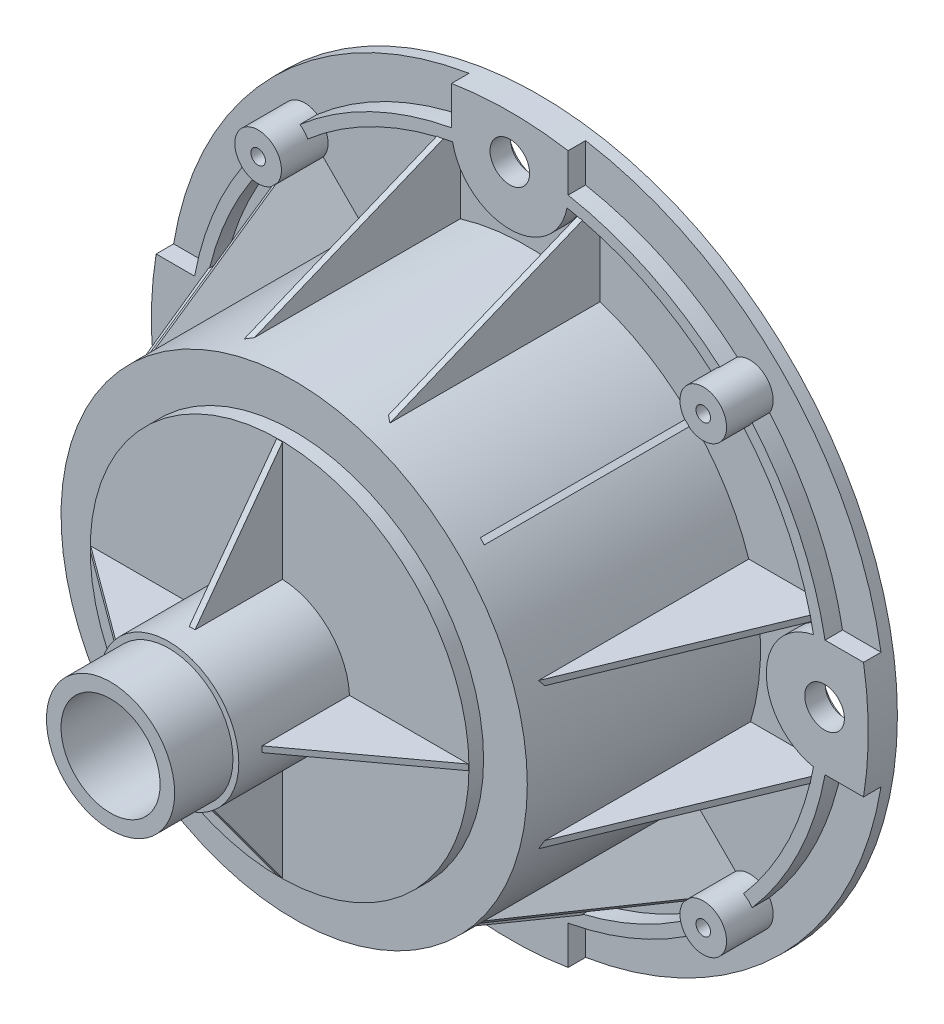
SolidWorks part; units mm, degrees
ref_plane "前视基准面" through (0, 0, 0) normal (0, 0, 1) x (1, 0, 0)
ref_plane "上视基准面" through (0, 0, 0) normal (0, 1, 0) x (1, 0, 0)
ref_plane "右视基准面" through (0, 0, 0) normal (1, 0, 0) x (0, 0, -1)
sketch "草图2" plane through (0, 0, 0) normal (0, 0, 1) x (1, 0, 0)
  circle A0 centre (0, 0) radius 40
  dimension "D1" = 80
extrude "凸台-拉伸1" add sketch "草图2" along normal blind 46
sketch "草图3" plane through (0, 0, 0) normal (0, 0, 1) x (1, 0, 0)
  circle A0 centre (0, 0) radius 61.5
  dimension "D1" = 123
extrude "凸台-拉伸2" add sketch "草图3" along normal blind 2 from offset 4
sketch "草图4" plane through (0, 0, 6) normal (0, 0, 1) x (1, 0, 0)
  line L0 (0, 69.5942) -> (0, 54) construction
  line L1 (0, -42.625) -> (0, 42.625) construction
  line L2 (10, 69.5942) -> (10, 54)
  line L3 (-10, 69.5942) -> (-10, 54)
  arc A0 (10, 69.5942) -> (-10, 69.5942) centre (0, 69.5942) ccw
  arc A1 (-10, 54) -> (10, 54) centre (0, 54) ccw
  point P5 (0, 61.7971)
  point P10 (0, 61.5366)
  circle M2 centre (0, 0) radius 61.5
  dimension "D1" = 10
  dimension "D2" = 54
extrude "凸台-拉伸3" add sketch "草图4" against normal blind 2 and the other way blind 3 contours L3 A1 L2 M2 region at (0, 53.5238, 6)
pattern_circular "阵列(圆周)1" count 4 over 360 about axis through (0, 0, 6) along (0, 0, 1) of "凸台-拉伸3"
sketch "草图5" plane through (0, 0, 6) normal (0, 0, 1) x (1, 0, 0)
  circle A0 centre (0, 0) radius 55
  dimension "D1" = 110
extrude "拉伸-薄壁1" add sketch "草图5" along normal blind 3 thin thin type one direction reverse wall 2
sketch "草图6" plane through (0, 0, 6) normal (0, 0, 1) x (1, 0, 0)
  line L0 (0, 0) -> (-38.1838, 38.1838) construction
  line L1 (0, -42.625) -> (0, 42.625) construction
  circle A0 centre (-38.1838, 38.1838) radius 4
  dimension "D3" = 8
  dimension "D1" = 54
  dimension "D2" = 45
extrude "凸台-拉伸4" add sketch "草图6" along normal blind 8
pattern_circular "阵列(圆周)2" count 4 over 360 about axis through (0, 0, 6) along (0, 0, 1) of "凸台-拉伸4"
sketch "草图7" plane through (0, 0, 46) normal (0, 0, 1) x (1, 0, 0)
  circle A0 centre (0, 0) radius 32.5
  dimension "D1" = 65
extrude "凸台-拉伸5" add sketch "草图7" along normal blind 2.5
sketch "草图8" plane through (0, 0, 0) normal (0, 0, -1) x (-1, 0, 0)
  circle A0 centre (0, 0) radius 38
  dimension "D1" = 76
extrude "切除-拉伸1" cut sketch "草图8" against normal blind 44
sketch "草图10" plane through (0, 0, 44) normal (0, 0, -1) x (-1, 0, 0)
  circle A3 centre (0, 0) radius 30.5
  circle A4 centre (0, 0) radius 30.5
  dimension "D1" = 2
extrude "切除-拉伸2" cut sketch "草图10" against normal blind 2.5
sketch "草图13" plane through (0, 0, 48.5) normal (0, 0, 1) x (1, 0, 0)
  circle A0 centre (0, 0) radius 12
  dimension "D1" = 24
extrude "凸台-拉伸7" add sketch "草图13" along normal blind 29 and the other way blind 5
sketch "草图14" plane through (0, 0, 77.5) normal (0, 0, 1) x (1, 0, 0)
  circle A0 centre (0, 0) radius 11
  dimension "D1" = 22
extrude "切除-拉伸3" cut sketch "草图14" against normal blind 10 flip side to cut
sketch "草图15" plane through (0, 0, 77.5) normal (0, 0, 1) x (1, 0, 0)
  circle A0 centre (0, 0) radius 8.5
  dimension "D1" = 17
extrude "切除-拉伸4" cut sketch "草图15" against normal through all
sketch "草图16" plane through (0, 0, 44) normal (0, 0, -1) x (-1, 0, 0)
  line L0 (0, 34.5) -> (0, 42.7884) construction
  line L1 (0, 42.625) -> (0, -42.625) construction
  line L2 (-1.5, 34.5) -> (-1.5, 42.7884)
  line L3 (1.5, 34.5) -> (1.5, 42.7884)
  circle A0 centre (0, 0) radius 34.5 construction
  arc A1 (-1.5, 34.5) -> (1.5, 34.5) centre (0, 34.5) ccw
  arc A2 (1.5, 42.7884) -> (-1.5, 42.7884) centre (0, 42.7884) ccw
  point P7 (0, 38.6442)
  circle M4 centre (0, 0) radius 38
  dimension "D1" = 69
  dimension "D2" = 3
extrude "凸台-拉伸8" add sketch "草图16" along normal blind 3 contours L2 A1 L3 M4 region at (0, 35.644, 44)
pattern_circular "阵列(圆周)3" count 8 over 360 about axis through (0, 0, 0) along (0, 0, 1) of "凸台-拉伸8"
sketch "草图17" plane through (0, 0, 0) normal (0, 1, 0) x (1, 0, 0)
  line L0 (12, -63.5) -> (32.4, -48.5)
  line L1 (12, -67.5) -> (12, -48.5) construction
  line L2 (-32.5, -48.5) -> (32.5, -48.5) construction
  point P6 (30.6418, -48.5)
  point P7 (32.5, -48.5)
  point P9 (32.1619, -48.5)
  dimension "D1" = 15
  dimension "D2" = 0.1
rib "筋1" sketch "草图17" sketch "草图17" thickness 1 extrusion direction parallel to sketch draft on no parameters "D1"=1
pattern_circular "阵列(圆周)4" count 4 over 360 about axis through (0, 0, 48.5) along (0, 0, 1) of "筋1"
ref_plane "基准面1" through (12, 0, 0) normal (1, 0, 0) x (0, 0, -1)
sketch "草图18" plane through (12, 0, 0) normal (1, 0, 0) x (0, 0, -1)
  line L0 (-42, 38.0324) -> (-9, 51.6236)
  line L4 (-46, 40) -> (-46, -40) construction
  point P2 (-41.6177, 35.7527)
  point P3 (-41.6638, 37.6625)
  point P7 (-42, 38.0324)
  dimension "D1" = 4
rib "筋2" sketch "草图18" sketch "草图18" thickness 1 extrusion direction parallel to sketch draft on no parameters "D1"=1
mirror "镜向1" about plane through (0, 0, 0) normal (1, 0, 0) of "筋2"
pattern_circular "阵列(圆周)5" count 4 over 360 about axis through (0, 0, 6) along (0, 0, 1) of "镜向1"
ref_axis "基准轴1" through (0, 0, 67.5) along (0, 0, 1)
ref_axis "基准轴2" through (38.1838, 38.1838, 14) along (0, 0, -1)
ref_plane "基准面2" through (0, 0, 0) normal (-0.7071, 0.7071, 0) x (0, 0, 1)
sketch "草图19" plane through (0, 0, 0) normal (-0.7071, 0.7071, 0) x (0, 0, 1)
  line L0 (42, 40) -> (14, 50.0828)
  line L1 (46, 40) -> (6, 40) construction
  line L2 (14, 50) -> (14, 58) construction
  line L3 (46, -40) -> (46, 40) construction
  point P8 (14, 51.0628)
  point P9 (14, 51.0455)
  point P10 (14, 50.0828)
  dimension "D1" = 4
rib "筋3" sketch "草图19" sketch "草图19" thickness 1 extrusion direction parallel to sketch draft on no parameters "D1"=1
pattern_circular "阵列(圆周)6" count 4 over 360 about axis through (0, 0, 6) along (0, 0, 1) of "筋3"
sketch "草图20" plane through (0, 0, 9) normal (0, 0, 1) x (1, 0, 0)
  circle A0 centre (54, 0) radius 3.4
  dimension "D1" = 6.8
extrude "切除-拉伸5" cut sketch "草图20" against normal through all
sketch "草图21" plane through (0, 0, 4) normal (0, 0, -1) x (-1, 0, 0)
  circle A0 centre (-54, 0) radius 5.25
  dimension "D1" = 10.5
extrude "切除-拉伸6" cut sketch "草图21" against normal blind 1.5
pattern_circular "阵列(圆周)7" count 4 over 360 about axis through (0, 0, 46) along (0, 0, -1) of "切除-拉伸6", "切除-拉伸5"
sketch "草图22" plane through (0, 0, 14) normal (0, 0, 1) x (1, 0, 0)
  circle A0 centre (-38.1838, 38.1838) radius 1.25
  dimension "D1" = 2.5
extrude "切除-拉伸7" cut sketch "草图22" against normal through all
pattern_circular "阵列(圆周)8" count 4 over 360 about axis through (0, 0, 6) along (0, 0, 1) of "切除-拉伸7"
